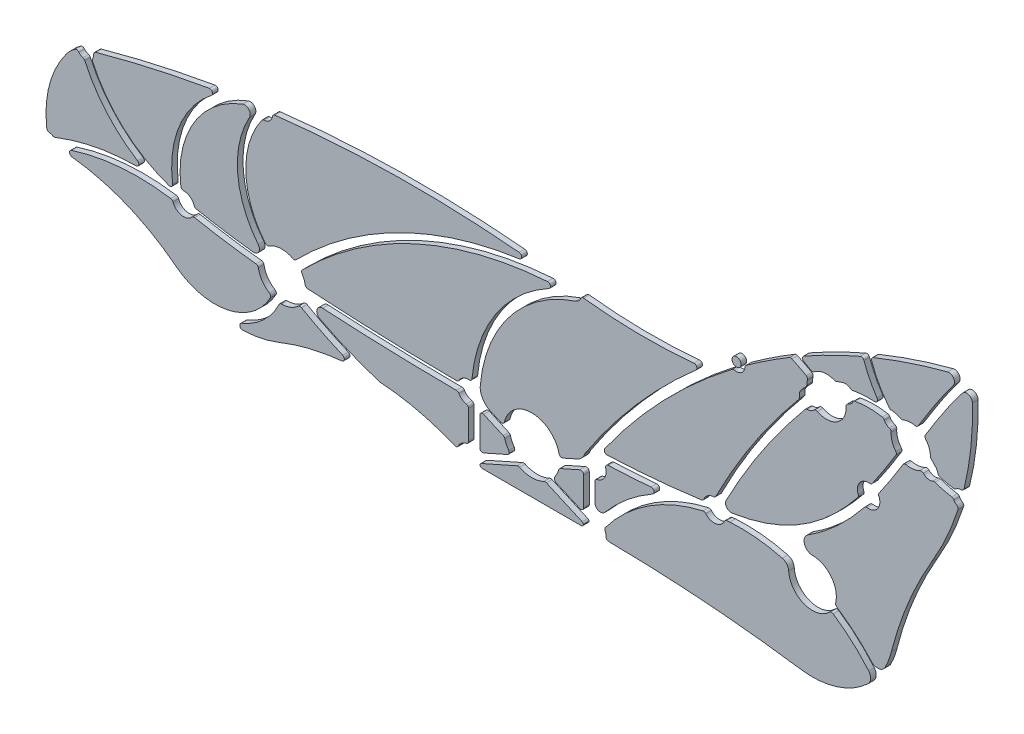
SolidWorks part; units mm, degrees
material "ｴﾎﾟｷｼ樹脂(充填剤なし)"
ref_plane "正面" through (0, 0, 0) normal (0, 0, 1) x (1, 0, 0)
ref_plane "平面" through (0, 0, 0) normal (0, 1, 0) x (1, 0, 0)
ref_plane "右側面" through (0, 0, 0) normal (1, 0, 0) x (0, 0, -1)
sketch "ｽｹｯﾁ1" plane through (0, 0, 0) normal (0, 0, 1) x (1, 0, 0)
  line L1 (-22.5, -10.101) -> (-22.5, 0.101)
  line L2 (-22.5, -10.101) -> (-22.5, 0.101)
  line L3 (22.5, 0.101) -> (22.5, -6.4126)
  line L4 (22.5, 0.101) -> (22.5, -6.4126)
  line L6 (11.119, 1.5832) -> (16.2024, 3.8425)
  line L7 (18.5, -10.042) -> (18.5, 0.042)
  line L8 (8.626, -7.1923) -> (17.0939, -10.9558)
  line L9 (17.0939, 0.9558) -> (10.1663, -2.1231)
  line L10 (18.5, -10.042) -> (18.5, 0.042)
  line L11 (8.626, -7.1923) -> (17.0939, -10.9558)
  line L12 (17.0939, 0.9558) -> (10.1663, -2.1231)
  line L13 (-10.1663, -2.1231) -> (-17.0939, 0.9558)
  line L14 (-17.0939, -10.9558) -> (-8.626, -7.1923)
  line L15 (-18.5, 0.042) -> (-18.5, -10.042)
  line L16 (-10.1663, -2.1231) -> (-17.0939, 0.9558)
  line L17 (-17.0939, -10.9558) -> (-8.626, -7.1923)
  line L18 (-18.5, 0.042) -> (-18.5, -10.042)
  line L19 (-17.5, -16) -> (17.5, -16)
  line L20 (-5.2366, -8.9688) -> (-17.9339, -14.6121)
  line L21 (17.9339, -14.6121) -> (5.2366, -8.9688)
  line L22 (-17.5, -16) -> (17.5, -16)
  line L23 (-5.2366, -8.9688) -> (-17.9339, -14.6121)
  line L24 (17.9339, -14.6121) -> (5.2366, -8.9688)
  line L25 (-14.7807, 3.2107) -> (-11.119, 1.5832)
  line L26 (11.119, 1.5832) -> (16.2024, 3.8425)
  line L27 (-14.7807, 3.2107) -> (-11.119, 1.5832)
  arc A16 (-103.3566, -14.0607) -> (-89.967, -1.5631) centre (-112.8701, 9.5532) ccw
  arc A17 (-89.0603, -0.9998) -> (-89.967, -1.5631) centre (-89.0674, -1.9998) ccw
  arc A18 (-89.0603, -0.9998) -> (-83.2113, 1.2758) centre (-89, 7.5) ccw
  arc A19 (-82.0317, 1.4104) -> (-83.2113, 1.2758) centre (-82.5302, 0.5435) ccw
  arc A20 (-82.0317, 1.4104) -> (-67.3468, -5.898) centre (-13.9413, 119.818) ccw
  arc A21 (-67.6378, -7.8134) -> (-67.3468, -5.898) centre (-67.7378, -6.8184) ccw
  arc A22 (-67.6378, -7.8134) -> (-90.1176, -13.3365) centre (-59.3978, -89.8605) ccw
  arc A23 (-102.9573, -15.9879) -> (-90.1176, -13.3365) centre (-103.9017, 21) ccw
  arc A24 (-103.3566, -14.0607) -> (-102.9573, -15.9879) centre (-102.9829, -14.9883) ccw
  arc A25 (-103.3566, -14.0607) -> (-89.967, -1.5631) centre (-112.8701, 9.5532) ccw
  arc A26 (-89.0603, -0.9998) -> (-89.967, -1.5631) centre (-89.0674, -1.9998) ccw
  arc A27 (-89.0603, -0.9998) -> (-83.2113, 1.2758) centre (-89, 7.5) ccw
  arc A28 (-82.0317, 1.4104) -> (-83.2113, 1.2758) centre (-82.5302, 0.5435) ccw
  arc A29 (-82.0317, 1.4104) -> (-67.3468, -5.898) centre (-13.9413, 119.818) ccw
  arc A30 (-67.6378, -7.8134) -> (-67.3468, -5.898) centre (-67.7378, -6.8184) ccw
  arc A31 (-67.6378, -7.8134) -> (-90.1176, -13.3365) centre (-59.3978, -89.8605) ccw
  arc A32 (-102.9573, -15.9879) -> (-90.1176, -13.3365) centre (-103.9017, 21) ccw
  arc A33 (-103.3566, -14.0607) -> (-102.9573, -15.9879) centre (-102.9829, -14.9883) ccw
  arc A35 (-114.85, 52.6669) -> (-155.2686, 43.5545) centre (-42.29, -363.3692) ccw
  arc A36 (-114.0595, 50.8962) -> (-114.85, 52.6669) centre (-114.6782, 51.6818) ccw
  arc A37 (-114.0595, 50.8962) -> (-127.9008, 16.5808) centre (-91.0356, 21.6602) ccw
  arc A38 (-126.7209, -8.1253) -> (-163.7257, 7.0322) centre (-172, -65.9175) ccw
  arc A39 (-163.9203, 8.9775) -> (-163.7257, 7.0322) centre (-163.613, 8.0259) ccw
  arc A40 (-128.5572, 11.8079) -> (-163.9203, 8.9775) centre (-140.2604, -64.3004) ccw
  arc A41 (-127.7673, 11.1556) -> (-128.5572, 11.8079) centre (-128.7091, 10.8195) ccw
  arc A42 (-127.7673, 11.1556) -> (-121.0036, 9.8502) centre (-124, 12.5) ccw
  arc A43 (-120.0633, 10.1693) -> (-121.0036, 9.8502) centre (-120.2545, 9.1877) ccw
  arc A44 (-120.0633, 10.1693) -> (-98.2474, 6.8503) centre (-69.0994, 271.8045) ccw
  arc A45 (-97.3718, 6.0294) -> (-98.2474, 6.8503) centre (-98.3567, 5.8563) ccw
  arc A46 (-97.3718, 6.0294) -> (-93.4427, 0.2535) centre (-89, 7.5) ccw
  arc A47 (-93.0844, -1.0722) -> (-93.4427, 0.2535) centre (-93.9654, -0.5991) ccw
  arc A48 (-126.7209, -8.1253) -> (-93.0844, -1.0722) centre (-112.8701, 9.5532) ccw
  arc A49 (-126.7209, -8.1253) -> (-163.7257, 7.0322) centre (-172, -65.9175) ccw
  arc A50 (-163.9203, 8.9775) -> (-163.7257, 7.0322) centre (-163.613, 8.0259) ccw
  arc A51 (-128.5572, 11.8079) -> (-163.9203, 8.9775) centre (-140.2604, -64.3004) ccw
  arc A52 (-127.7673, 11.1556) -> (-128.5572, 11.8079) centre (-128.7091, 10.8195) ccw
  arc A53 (-127.7673, 11.1556) -> (-121.0036, 9.8502) centre (-124, 12.5) ccw
  arc A54 (-120.0633, 10.1693) -> (-121.0036, 9.8502) centre (-120.2545, 9.1877) ccw
  arc A55 (-120.0633, 10.1693) -> (-98.2474, 6.8503) centre (-69.0994, 271.8045) ccw
  arc A56 (-97.3718, 6.0294) -> (-98.2474, 6.8503) centre (-98.3567, 5.8563) ccw
  arc A57 (-97.3718, 6.0294) -> (-93.4427, 0.2535) centre (-89, 7.5) ccw
  arc A58 (-93.0844, -1.0722) -> (-93.4427, 0.2535) centre (-93.9654, -0.5991) ccw
  arc A59 (-126.7209, -8.1253) -> (-93.0844, -1.0722) centre (-112.8701, 9.5532) ccw
  arc A60 (-129.2172, 15.4989) -> (-127.9008, 16.5808) centre (-128.8914, 16.4443) ccw
  arc A61 (-156.4002, 40.1644) -> (-129.2172, 15.4989) centre (-114.0417, 59.5347) ccw
  arc A62 (-156.3681, 41.0602) -> (-156.4002, 40.1644) centre (-155.4908, 40.5803) ccw
  arc A63 (-156.3681, 41.0602) -> (-156.0008, 42.5682) centre (-159, 42.5) ccw
  arc A64 (-155.2686, 43.5545) -> (-156.0008, 42.5682) centre (-155.001, 42.5909) ccw
  arc A65 (-114.85, 52.6669) -> (-155.2686, 43.5545) centre (-42.29, -363.3692) ccw
  arc A66 (-114.0595, 50.8962) -> (-114.85, 52.6669) centre (-114.6782, 51.6818) ccw
  arc A67 (-114.0595, 50.8962) -> (-127.9008, 16.5808) centre (-91.0356, 21.6602) ccw
  arc A68 (-129.2172, 15.4989) -> (-127.9008, 16.5808) centre (-128.8914, 16.4443) ccw
  arc A69 (-156.4002, 40.1644) -> (-129.2172, 15.4989) centre (-114.0417, 59.5347) ccw
  arc A70 (-156.3681, 41.0602) -> (-156.4002, 40.1644) centre (-155.4908, 40.5803) ccw
  arc A71 (-156.3681, 41.0602) -> (-156.0008, 42.5682) centre (-159, 42.5) ccw
  arc A72 (-155.2686, 43.5545) -> (-156.0008, 42.5682) centre (-155.001, 42.5909) ccw
  arc A73 (-100.5051, 50.879) -> (-97.4246, 13.2154) centre (-71.0713, 34.3286) ccw
  arc A74 (-99.214, 9.978) -> (-97.4246, 13.2154) centre (-98.9855, 11.9649) ccw
  arc A75 (-4.471, 57.2503) -> (-91.4838, 56.0721) centre (-42.29, -363.3692) ccw
  arc A76 (-140.9263, 15.6997) -> (-169.717, 10.0822) centre (-140.2604, -64.3004) ccw
  arc A77 (-170.5639, 10.1339) -> (-169.717, 10.0822) centre (-170.0852, 11.0119) ccw
  arc A78 (-170.5639, 10.1339) -> (-171.786, 10.4924) centre (-172, 7.5) ccw
  arc A79 (-172.7066, 11.3632) -> (-171.786, 10.4924) centre (-171.7146, 11.4898) ccw
  arc A80 (-165.6353, 37.9447) -> (-172.7066, 11.3632) centre (-136.5587, 15.9784) ccw
  arc A81 (-162.6526, 40.7855) -> (-165.6353, 37.9447) centre (-155.4945, 30.2837) ccw
  arc A82 (-161.317, 40.5944) -> (-162.6526, 40.7855) centre (-162.0894, 39.9592) ccw
  arc A83 (-161.317, 40.5944) -> (-159.8316, 39.6176) centre (-159, 42.5) ccw
  arc A84 (-159.198, 39.0695) -> (-159.8316, 39.6176) centre (-160.1088, 38.6568) ccw
  arc A85 (-159.198, 39.0695) -> (-140.4029, 17.5466) centre (-114.0417, 59.5347) ccw
  arc A86 (-140.9263, 15.6997) -> (-140.4029, 17.5466) centre (-140.9346, 16.6997) ccw
  arc A87 (-140.9263, 15.6997) -> (-169.717, 10.0822) centre (-140.2604, -64.3004) ccw
  arc A88 (-170.5639, 10.1339) -> (-169.717, 10.0822) centre (-170.0852, 11.0119) ccw
  arc A89 (-170.5639, 10.1339) -> (-171.786, 10.4924) centre (-172, 7.5) ccw
  arc A90 (-172.7066, 11.3632) -> (-171.786, 10.4924) centre (-171.7146, 11.4898) ccw
  arc A91 (-165.6353, 37.9447) -> (-172.7066, 11.3632) centre (-136.5587, 15.9784) ccw
  arc A92 (-162.6526, 40.7855) -> (-165.6353, 37.9447) centre (-155.4945, 30.2837) ccw
  arc A93 (-161.317, 40.5944) -> (-162.6526, 40.7855) centre (-162.0894, 39.9592) ccw
  arc A94 (-161.317, 40.5944) -> (-159.8316, 39.6176) centre (-159, 42.5) ccw
  arc A95 (-159.198, 39.0695) -> (-159.8316, 39.6176) centre (-160.1088, 38.6568) ccw
  arc A96 (-159.198, 39.0695) -> (-140.4029, 17.5466) centre (-114.0417, 59.5347) ccw
  arc A97 (-140.9263, 15.6997) -> (-140.4029, 17.5466) centre (-140.9346, 16.6997) ccw
  arc A98 (-4.4224, 55.2639) -> (-4.471, 57.2503) centre (-4.5606, 56.2543) ccw
  arc A99 (-4.4224, 55.2639) -> (-83.9236, 15.238) centre (14.6672, -81.6202) ccw
  arc A100 (-85.0963, 15.0506) -> (-83.9236, 15.238) centre (-84.637, 15.9389) ccw
  arc A101 (-85.0963, 15.0506) -> (-93.5868, 14.6562) centre (-89, 7.5) ccw
  arc A102 (-94.9009, 14.8656) -> (-93.5868, 14.6562) centre (-94.1264, 15.4981) ccw
  arc A103 (-96.1287, 52.1831) -> (-94.9009, 14.8656) centre (-71.0713, 34.3286) ccw
  arc A104 (-95.319, 52.6028) -> (-96.1287, 52.1831) centre (-95.3143, 51.6028) ccw
  arc A105 (-95.319, 52.6028) -> (-92.3587, 55.2099) centre (-95.3328, 55.6027) ccw
  arc A106 (-91.4838, 56.0721) -> (-92.3587, 55.2099) centre (-91.3673, 55.0789) ccw
  arc A107 (-4.471, 57.2503) -> (-91.4838, 56.0721) centre (-42.29, -363.3692) ccw
  arc A108 (-4.4224, 55.2639) -> (-4.471, 57.2503) centre (-4.5606, 56.2543) ccw
  arc A109 (-4.4224, 55.2639) -> (-83.9236, 15.238) centre (14.6672, -81.6202) ccw
  arc A110 (-85.0963, 15.0506) -> (-83.9236, 15.238) centre (-84.637, 15.9389) ccw
  arc A111 (-85.0963, 15.0506) -> (-93.5868, 14.6562) centre (-89, 7.5) ccw
  arc A112 (-94.9009, 14.8656) -> (-93.5868, 14.6562) centre (-94.1264, 15.4981) ccw
  arc A113 (-96.1287, 52.1831) -> (-94.9009, 14.8656) centre (-71.0713, 34.3286) ccw
  arc A114 (-95.319, 52.6028) -> (-96.1287, 52.1831) centre (-95.3143, 51.6028) ccw
  arc A115 (-95.319, 52.6028) -> (-92.3587, 55.2099) centre (-95.3328, 55.6027) ccw
  arc A116 (-91.4838, 56.0721) -> (-92.3587, 55.2099) centre (-91.3673, 55.0789) ccw
  arc A117 (-22.314, 8.9957) -> (-25.9592, 7.0085) centre (-22.5, 5) ccw
  arc A118 (-26.8289, 6.5106) -> (-25.9592, 7.0085) centre (-26.824, 7.5106) ccw
  arc A119 (-79.7472, 8.3552) -> (-26.8289, 6.5106) centre (-22.5, 890.7) ccw
  arc A120 (-80.6633, 9.158) -> (-79.7472, 8.3552) centre (-79.6825, 9.3531) ccw
  arc A121 (-80.6633, 9.158) -> (-81.8017, 12.0204) centre (-89, 7.5) ccw
  arc A122 (-81.6673, 13.2539) -> (-81.8017, 12.0204) centre (-80.9548, 12.5522) ccw
  arc A123 (5.6096, 53.2849) -> (-81.6673, 13.2539) centre (14.6672, -81.6202) ccw
  arc A124 (6.1525, 51.4076) -> (5.6096, 53.2849) centre (5.6766, 52.2871) ccw
  arc A125 (6.1525, 51.4076) -> (-21.2718, 9.9017) centre (31.2679, 5) ccw
  arc A126 (-22.314, 8.9957) -> (-21.2718, 9.9017) centre (-22.2675, 9.9946) ccw
  arc A127 (-22.314, 8.9957) -> (-25.9592, 7.0085) centre (-22.5, 5) ccw
  arc A128 (-26.8289, 6.5106) -> (-25.9592, 7.0085) centre (-26.824, 7.5106) ccw
  arc A129 (-79.7472, 8.3552) -> (-26.8289, 6.5106) centre (-22.5, 890.7) ccw
  arc A130 (-80.6633, 9.158) -> (-79.7472, 8.3552) centre (-79.6825, 9.3531) ccw
  arc A131 (-80.6633, 9.158) -> (-81.8017, 12.0204) centre (-89, 7.5) ccw
  arc A132 (-81.6673, 13.2539) -> (-81.8017, 12.0204) centre (-80.9548, 12.5522) ccw
  arc A133 (5.6096, 53.2849) -> (-81.6673, 13.2539) centre (14.6672, -81.6202) ccw
  arc A134 (6.1525, 51.4076) -> (5.6096, 53.2849) centre (5.6766, 52.2871) ccw
  arc A135 (6.1525, 51.4076) -> (-21.2718, 9.9017) centre (31.2679, 5) ccw
  arc A136 (-22.314, 8.9957) -> (-21.2718, 9.9017) centre (-22.2675, 9.9946) ccw
  arc A137 (-119.4498, 13.1062) -> (-99.214, 9.978) centre (-69.0994, 271.8045) ccw
  arc A138 (-27.4366, -13.8466) -> (-54.0639, -7.5734) centre (-59.3978, -89.8605) ccw
  arc A139 (-54.3014, -7.5287) -> (-54.0639, -7.5734) centre (-53.9993, -6.5755) ccw
  arc A140 (-75.487, 1.2505) -> (-54.3014, -7.5287) centre (-13.9413, 119.818) ccw
  arc A141 (-74.4485, 5.0222) -> (-75.487, 1.2505) centre (-74.5656, 3.0256) ccw
  arc A142 (-74.4485, 5.0222) -> (-26.8313, 3.5106) centre (-22.5, 890.7) ccw
  arc A143 (-25.969, 3.0085) -> (-26.8313, 3.5106) centre (-26.8362, 2.5106) ccw
  arc A144 (-25.969, 3.0085) -> (-23.3, 1.0808) centre (-22.5, 5) ccw
  arc A145 (-22.5, 0.101) -> (-23.3, 1.0808) centre (-23.5, 0.101) ccw
  arc A146 (-23.3, -11.0808) -> (-22.5, -10.101) centre (-23.5, -10.101) ccw
  arc A147 (-23.3, -11.0808) -> (-26.1392, -13.3399) centre (-22.5, -15) ccw
  arc A148 (-27.4366, -13.8466) -> (-26.1392, -13.3399) centre (-27.049, -12.9248) ccw
  arc A149 (-27.4366, -13.8466) -> (-54.0639, -7.5734) centre (-59.3978, -89.8605) ccw
  arc A150 (-54.3014, -7.5287) -> (-54.0639, -7.5734) centre (-53.9993, -6.5755) ccw
  arc A151 (-75.487, 1.2505) -> (-54.3014, -7.5287) centre (-13.9413, 119.818) ccw
  arc A152 (-74.4485, 5.0222) -> (-75.487, 1.2505) centre (-74.5656, 3.0256) ccw
  arc A153 (-74.4485, 5.0222) -> (-26.8313, 3.5106) centre (-22.5, 890.7) ccw
  arc A154 (-25.969, 3.0085) -> (-26.8313, 3.5106) centre (-26.8362, 2.5106) ccw
  arc A155 (-25.969, 3.0085) -> (-23.3, 1.0808) centre (-22.5, 5) ccw
  arc A156 (-22.5, 0.101) -> (-23.3, 1.0808) centre (-23.5, 0.101) ccw
  arc A157 (-23.3, -11.0808) -> (-22.5, -10.101) centre (-23.5, -10.101) ccw
  arc A158 (-23.3, -11.0808) -> (-26.1392, -13.3399) centre (-22.5, -15) ccw
  arc A159 (-27.4366, -13.8466) -> (-26.1392, -13.3399) centre (-27.049, -12.9248) ccw
  arc A160 (-120.207, 13.7702) -> (-119.4498, 13.1062) centre (-119.2588, 14.0878) ccw
  arc A161 (-120.207, 13.7702) -> (-123.99, 16.5) centre (-124, 12.5) ccw
  arc A162 (-124.9796, 17.3747) -> (-123.99, 16.5) centre (-123.9875, 17.5) ccw
  arc A163 (-102.9446, 53.7342) -> (-124.9796, 17.3747) centre (-91.0356, 21.6602) ccw
  arc A164 (-100.5051, 50.879) -> (-102.9446, 53.7342) centre (-102.2484, 51.8592) ccw
  arc A165 (-100.5051, 50.879) -> (-97.4246, 13.2154) centre (-71.0713, 34.3286) ccw
  arc A166 (-99.214, 9.978) -> (-97.4246, 13.2154) centre (-98.9855, 11.9649) ccw
  arc A167 (-119.4498, 13.1062) -> (-99.214, 9.978) centre (-69.0994, 271.8045) ccw
  arc A168 (-120.207, 13.7702) -> (-119.4498, 13.1062) centre (-119.2588, 14.0878) ccw
  arc A169 (-120.207, 13.7702) -> (-123.99, 16.5) centre (-124, 12.5) ccw
  arc A170 (-124.9796, 17.3747) -> (-123.99, 16.5) centre (-123.9875, 17.5) ccw
  arc A171 (-102.9446, 53.7342) -> (-124.9796, 17.3747) centre (-91.0356, 21.6602) ccw
  arc A172 (-100.5051, 50.879) -> (-102.9446, 53.7342) centre (-102.2484, 51.8592) ccw
  arc A180 (17.0939, -10.9558) -> (18.5, -10.042) centre (17.5, -10.042) ccw
  arc A181 (8.2111, -5.7077) -> (8.626, -7.1923) centre (9.0322, -6.2785) ccw
  arc A182 (22.5, -6.4126) -> (26.0294, -7.7013) centre (24.5, -6.4126) ccw
  arc A183 (23.3, 1.0808) -> (22.5, 0.101) centre (23.5, 0.101) ccw
  arc A184 (23.3, 1.0808) -> (26.3403, 6.1191) centre (22.5, 5) ccw
  arc A185 (27.2601, 7.398) -> (26.3403, 6.1191) centre (27.3003, 6.3988) ccw
  arc A186 (27.2601, 7.398) -> (42.5161, 8.3479) centre (13.2682, 355.1295) ccw
  arc A187 (43.0938, 6.4818) -> (42.5161, 8.3479) centre (42.6001, 7.3514) ccw
  arc A188 (107.7452, 73.9205) -> (100.6016, 72.9268) centre (105, 67.4812) ccw
  arc A189 (99.4771, 72.8365) -> (100.6016, 72.9268) centre (99.9733, 73.7047) ccw
  arc A190 (99.4771, 72.8365) -> (96.9768, 74.198) centre (65, 12.5) ccw
  arc A191 (96.9469, 75.9576) -> (96.9768, 74.198) centre (97.4369, 75.0859) ccw
  arc A192 (116.993, 85.9037) -> (96.9469, 75.9576) centre (203.2901, -113.1988) ccw
  arc A193 (118.3344, 85.3171) -> (116.993, 85.9037) centre (117.3907, 84.9862) ccw
  arc A194 (118.3344, 85.3171) -> (122.9876, 76.0572) centre (156.5, 98.6967) ccw
  arc A195 (122.0896, 74.4999) -> (122.9876, 76.0572) centre (122.1589, 75.4974) ccw
  arc A196 (122.0896, 74.4999) -> (114.3306, 74.0344) centre (120, 44.4324) ccw
  arc A197 (113.5331, 74.2236) -> (114.3306, 74.0344) centre (114.1425, 75.0165) ccw
  arc A198 (113.5331, 74.2236) -> (110.8362, 74.7163) centre (111.7051, 71.8449) ccw
  arc A199 (110.8362, 74.7163) -> (108.5008, 73.9088) centre (120, 44.4324) ccw
  arc A200 (107.7452, 73.9205) -> (108.5008, 73.9088) centre (108.1373, 74.8404) ccw
  arc A201 (107.7452, 73.9205) -> (100.6016, 72.9268) centre (105, 67.4812) ccw
  arc A202 (99.4771, 72.8365) -> (100.6016, 72.9268) centre (99.9733, 73.7047) ccw
  arc A203 (99.4771, 72.8365) -> (96.9768, 74.198) centre (65, 12.5) ccw
  arc A204 (96.9469, 75.9576) -> (96.9768, 74.198) centre (97.4369, 75.0859) ccw
  arc A205 (116.993, 85.9037) -> (96.9469, 75.9576) centre (203.2901, -113.1988) ccw
  arc A206 (118.3344, 85.3171) -> (116.993, 85.9037) centre (117.3907, 84.9862) ccw
  arc A207 (118.3344, 85.3171) -> (122.9876, 76.0572) centre (156.5, 98.6967) ccw
  arc A208 (122.0896, 74.4999) -> (122.9876, 76.0572) centre (122.1589, 75.4974) ccw
  arc A209 (122.0896, 74.4999) -> (114.3306, 74.0344) centre (120, 44.4324) ccw
  arc A210 (113.5331, 74.2236) -> (114.3306, 74.0344) centre (114.1425, 75.0165) ccw
  arc A211 (113.5331, 74.2236) -> (110.8362, 74.7163) centre (111.7051, 71.8449) ccw
  arc A212 (110.8362, 74.7163) -> (108.5008, 73.9088) centre (120, 44.4324) ccw
  arc A213 (107.7452, 73.9205) -> (108.5008, 73.9088) centre (108.1373, 74.8404) ccw
  arc A214 (43.0938, 6.4818) -> (26.0294, -7.7013) centre (74.1755, -48.2713) ccw
  arc A215 (22.5, -6.4126) -> (26.0294, -7.7013) centre (24.5, -6.4126) ccw
  arc A216 (23.3, 1.0808) -> (22.5, 0.101) centre (23.5, 0.101) ccw
  arc A217 (23.3, 1.0808) -> (26.3403, 6.1191) centre (22.5, 5) ccw
  arc A218 (89.2736, 9.7568) -> (70.6226, 11.5834) centre (74.1755, -48.2713) ccw
  arc A219 (91.5134, 7.0221) -> (89.2736, 9.7568) centre (88.5182, 6.8535) ccw
  arc A220 (91.5134, 7.0221) -> (106.0705, 1.5503) centre (100, 7.5) ccw
  arc A221 (107.3377, 1.6835) -> (106.0705, 1.5503) centre (106.7847, 0.8503) ccw
  arc A222 (120.0008, -9.6028) -> (107.3377, 1.6835) centre (74.1755, -48.2713) ccw
  arc A223 (119.7512, -13.7341) -> (120.0008, -9.6028) centre (117.708, -11.5375) ccw
  arc A224 (95.9045, -21.2094) -> (119.7512, -13.7341) centre (100, 7.5) ccw
  arc A225 (95.9045, -21.2094) -> (27.4903, -16.024) centre (22.5, -535.7727) ccw
  arc A226 (26.5, -15.0192) -> (27.4903, -16.024) centre (27.4999, -15.024) ccw
  arc A227 (26.5, -15.0192) -> (26.1198, -13.2978) centre (22.5, -15) ccw
  arc A228 (26.225, -12.2719) -> (26.1198, -13.2978) centre (27.0247, -12.8723) ccw
  arc A229 (60.9851, 10.2199) -> (26.225, -12.2719) centre (74.1755, -48.2713) ccw
  arc A230 (61.9641, 9.8955) -> (60.9851, 10.2199) centre (61.2051, 9.2444) ccw
  arc A231 (61.9641, 9.8955) -> (68.6438, 10.85) centre (65, 12.5) ccw
  arc A232 (69.4318, 11.4299) -> (68.6438, 10.85) centre (69.5548, 10.4374) ccw
  arc A233 (69.4318, 11.4299) -> (70.5449, 11.5758) centre (59.6347, 90.4932) ccw
  arc A234 (70.6226, 11.5834) -> (70.5449, 11.5758) centre (70.6819, 10.5852) ccw
  arc A235 (89.2736, 9.7568) -> (70.6226, 11.5834) centre (74.1755, -48.2713) ccw
  arc A236 (91.5134, 7.0221) -> (89.2736, 9.7568) centre (88.5182, 6.8535) ccw
  arc A237 (91.5134, 7.0221) -> (106.0705, 1.5503) centre (100, 7.5) ccw
  arc A238 (107.3377, 1.6835) -> (106.0705, 1.5503) centre (106.7847, 0.8503) ccw
  arc A239 (120.0008, -9.6028) -> (107.3377, 1.6835) centre (74.1755, -48.2713) ccw
  arc A240 (119.7512, -13.7341) -> (120.0008, -9.6028) centre (117.708, -11.5375) ccw
  arc A241 (95.9045, -21.2094) -> (119.7512, -13.7341) centre (100, 7.5) ccw
  arc A242 (95.9045, -21.2094) -> (27.4903, -16.024) centre (22.5, -535.7727) ccw
  arc A243 (26.5, -15.0192) -> (27.4903, -16.024) centre (27.4999, -15.024) ccw
  arc A244 (26.5, -15.0192) -> (26.1198, -13.2978) centre (22.5, -15) ccw
  arc A245 (26.225, -12.2719) -> (26.1198, -13.2978) centre (27.0247, -12.8723) ccw
  arc A246 (60.9851, 10.2199) -> (26.225, -12.2719) centre (74.1755, -48.2713) ccw
  arc A247 (61.9641, 9.8955) -> (60.9851, 10.2199) centre (61.2051, 9.2444) ccw
  arc A248 (61.9641, 9.8955) -> (68.6438, 10.85) centre (65, 12.5) ccw
  arc A249 (69.4318, 11.4299) -> (68.6438, 10.85) centre (69.5548, 10.4374) ccw
  arc A250 (69.4318, 11.4299) -> (70.5449, 11.5758) centre (59.6347, 90.4932) ccw
  arc A251 (70.6226, 11.5834) -> (70.5449, 11.5758) centre (70.6819, 10.5852) ccw
  arc A252 (27.2601, 7.398) -> (26.3403, 6.1191) centre (27.3003, 6.3988) ccw
  arc A253 (27.2601, 7.398) -> (42.5161, 8.3479) centre (13.2682, 355.1295) ccw
  arc A254 (71.3431, 59.0772) -> (26.022, 11.9612) centre (203.2901, -113.1988) ccw
  arc A255 (72.1979, 59.2524) -> (71.3431, 59.0772) centre (71.9512, 58.2833) ccw
  arc A256 (72.1979, 59.2524) -> (75.9352, 62.0305) centre (72.938, 62.1596) ccw
  arc A257 (76.3493, 62.7985) -> (75.9352, 62.0305) centre (76.9343, 61.9874) ccw
  arc A258 (91.7165, 72.9204) -> (76.3493, 62.7985) centre (203.2901, -113.1988) ccw
  arc A259 (92.6465, 72.9722) -> (91.7165, 72.9204) centre (92.2307, 72.0627) ccw
  arc A260 (97.7506, 70.3671) -> (92.6465, 72.9722) centre (65, 12.5) ccw
  arc A261 (98.2258, 69.2449) -> (97.7506, 70.3671) centre (97.2581, 69.4969) ccw
  arc A262 (98.2258, 69.2449) -> (98.0007, 67.5789) centre (105, 67.4812) ccw
  arc A263 (97.7054, 66.8832) -> (98.0007, 67.5789) centre (97.0008, 67.5928) ccw
  arc A264 (97.7054, 66.8832) -> (96.0213, 65.0748) centre (120, 44.4324) ccw
  arc A265 (96.0213, 65.0748) -> (95.3497, 62.5466) centre (98.2949, 63.1176) ccw
  arc A266 (95.1344, 61.7139) -> (95.3497, 62.5466) centre (94.368, 62.3562) ccw
  arc A267 (95.1344, 61.7139) -> (65.5834, 17.0366) centre (276.8279, -90.5756) ccw
  arc A268 (64.7539, 16.4924) -> (65.5834, 17.0366) centre (64.6924, 17.4905) ccw
  arc A269 (64.7539, 16.4924) -> (61.2853, 13.9837) centre (65, 12.5) ccw
  arc A270 (60.4936, 13.364) -> (61.2853, 13.9837) centre (60.3567, 14.3546) ccw
  arc A271 (26.8783, 10.3852) -> (60.4936, 13.364) centre (13.2682, 355.1295) ccw
  arc A272 (26.022, 11.9612) -> (26.8783, 10.3852) centre (26.8389, 11.3844) ccw
  arc A273 (71.3431, 59.0772) -> (26.022, 11.9612) centre (203.2901, -113.1988) ccw
  arc A274 (72.1979, 59.2524) -> (71.3431, 59.0772) centre (71.9512, 58.2833) ccw
  arc A275 (72.1979, 59.2524) -> (75.9352, 62.0305) centre (72.938, 62.1596) ccw
  arc A276 (76.3493, 62.7985) -> (75.9352, 62.0305) centre (76.9343, 61.9874) ccw
  arc A277 (91.7165, 72.9204) -> (76.3493, 62.7985) centre (203.2901, -113.1988) ccw
  arc A278 (92.6465, 72.9722) -> (91.7165, 72.9204) centre (92.2307, 72.0627) ccw
  arc A279 (97.7506, 70.3671) -> (92.6465, 72.9722) centre (65, 12.5) ccw
  arc A280 (98.2258, 69.2449) -> (97.7506, 70.3671) centre (97.2581, 69.4969) ccw
  arc A281 (98.2258, 69.2449) -> (98.0007, 67.5789) centre (105, 67.4812) ccw
  arc A282 (97.7054, 66.8832) -> (98.0007, 67.5789) centre (97.0008, 67.5928) ccw
  arc A283 (97.7054, 66.8832) -> (96.0213, 65.0748) centre (120, 44.4324) ccw
  arc A284 (96.0213, 65.0748) -> (95.3497, 62.5466) centre (98.2949, 63.1176) ccw
  arc A285 (95.1344, 61.7139) -> (95.3497, 62.5466) centre (94.368, 62.3562) ccw
  arc A286 (95.1344, 61.7139) -> (65.5834, 17.0366) centre (276.8279, -90.5756) ccw
  arc A287 (64.7539, 16.4924) -> (65.5834, 17.0366) centre (64.6924, 17.4905) ccw
  arc A288 (64.7539, 16.4924) -> (61.2853, 13.9837) centre (65, 12.5) ccw
  arc A289 (60.4936, 13.364) -> (61.2853, 13.9837) centre (60.3567, 14.3546) ccw
  arc A290 (26.8783, 10.3852) -> (60.4936, 13.364) centre (13.2682, 355.1295) ccw
  arc A291 (26.022, 11.9612) -> (26.8783, 10.3852) centre (26.8389, 11.3844) ccw
  arc A292 (43.0938, 6.4818) -> (42.5161, 8.3479) centre (42.6001, 7.3514) ccw
  arc A293 (43.0938, 6.4818) -> (26.0294, -7.7013) centre (74.1755, -48.2713) ccw
  arc A294 (8.2111, -5.7077) -> (9.6113, -2.7608) centre (0, 0) ccw
  arc A295 (10.1663, -2.1231) -> (9.6113, -2.7608) centre (10.5725, -3.0369) ccw
  arc A296 (18.5, 0.042) -> (17.0939, 0.9558) centre (17.5, 0.042) ccw
  arc A297 (148.0871, 96.6622) -> (121.6343, 87.8518) centre (203.2901, -113.1988) ccw
  arc A298 (150.1845, 93.5129) -> (148.0871, 96.6622) centre (148.5959, 94.728) ccw
  arc A302 (136.5337, 74.3112) -> (137.605, 74.7637) centre (136.7528, 75.2869) ccw
  arc A303 (136.5337, 74.3112) -> (132.2548, 73.9205) centre (135, 67.4812) ccw
  arc A304 (131.4992, 73.9088) -> (132.2548, 73.9205) centre (131.8627, 74.8404) ccw
  arc A305 (131.4992, 73.9088) -> (129.1638, 74.7163) centre (120, 44.4324) ccw
  arc A306 (129.1638, 74.7163) -> (128.1602, 74.8418) centre (128.2949, 71.8449) ccw
  arc A307 (127.3364, 75.2137) -> (128.1602, 74.8418) centre (128.1152, 75.8408) ccw
  arc A308 (69.2612, 17.6244) -> (71.3386, 14.7231) centre (71.0347, 16.6999) ccw
  arc A309 (97.4124, 59.7615) -> (69.2612, 17.6244) centre (276.8279, -90.5756) ccw
  arc A310 (98.2079, 60.1189) -> (97.4124, 59.7615) centre (98.1789, 59.1193) ccw
  arc A311 (98.2079, 60.1189) -> (100.5079, 61.0921) centre (98.2949, 63.1176) ccw
  arc A312 (101.7149, 61.3) -> (100.5079, 61.0921) centre (101.2456, 60.4169) ccw
  arc A313 (101.7149, 61.3) -> (111.9821, 67.9818) centre (105, 67.4812) ccw
  arc A314 (112.6609, 69.0012) -> (111.9821, 67.9818) centre (112.9795, 68.0533) ccw
  arc A315 (112.6609, 69.0012) -> (114.4231, 70.575) centre (111.7051, 71.8449) ccw
  arc A316 (115.1504, 71.1356) -> (114.4231, 70.575) centre (115.3291, 70.1517) ccw
  arc A317 (124.8496, 71.1356) -> (115.1504, 71.1356) centre (120, 44.4324) ccw
  arc A318 (125.5769, 70.575) -> (124.8496, 71.1356) centre (124.6709, 70.1517) ccw
  arc A319 (125.5769, 70.575) -> (127.3391, 69.0012) centre (128.2949, 71.8449) ccw
  arc A320 (128.0179, 67.9818) -> (127.3391, 69.0012) centre (127.0205, 68.0533) ccw
  arc A321 (128.0179, 67.9818) -> (129.6405, 62.9784) centre (135, 67.4812) ccw
  arc A322 (129.7265, 61.811) -> (129.6405, 62.9784) centre (128.8749, 62.3351) ccw
  arc A323 (120.3745, 48.4148) -> (121.2864, 48.8356) centre (120.4681, 49.4104) ccw
  arc A324 (120.3745, 48.4148) -> (116.2864, 42.9461) centre (120, 44.4324) ccw
  arc A325 (116.1386, 41.9495) -> (116.2864, 42.9461) centre (115.358, 42.5745) ccw
  arc A326 (69.2612, 17.6244) -> (71.3386, 14.7231) centre (71.0347, 16.6999) ccw
  arc A327 (97.4124, 59.7615) -> (69.2612, 17.6244) centre (276.8279, -90.5756) ccw
  arc A328 (98.2079, 60.1189) -> (97.4124, 59.7615) centre (98.1789, 59.1193) ccw
  arc A329 (98.2079, 60.1189) -> (100.5079, 61.0921) centre (98.2949, 63.1176) ccw
  arc A330 (101.7149, 61.3) -> (100.5079, 61.0921) centre (101.2456, 60.4169) ccw
  arc A331 (101.7149, 61.3) -> (111.9821, 67.9818) centre (105, 67.4812) ccw
  arc A332 (112.6609, 69.0012) -> (111.9821, 67.9818) centre (112.9795, 68.0533) ccw
  arc A333 (112.6609, 69.0012) -> (114.4231, 70.575) centre (111.7051, 71.8449) ccw
  arc A334 (115.1504, 71.1356) -> (114.4231, 70.575) centre (115.3291, 70.1517) ccw
  arc A335 (124.8496, 71.1356) -> (115.1504, 71.1356) centre (120, 44.4324) ccw
  arc A336 (125.5769, 70.575) -> (124.8496, 71.1356) centre (124.6709, 70.1517) ccw
  arc A337 (125.5769, 70.575) -> (127.3391, 69.0012) centre (128.2949, 71.8449) ccw
  arc A338 (128.0179, 67.9818) -> (127.3391, 69.0012) centre (127.0205, 68.0533) ccw
  arc A339 (128.0179, 67.9818) -> (129.6405, 62.9784) centre (135, 67.4812) ccw
  arc A340 (129.7265, 61.811) -> (129.6405, 62.9784) centre (128.8749, 62.3351) ccw
  arc A341 (120.3745, 48.4148) -> (121.2864, 48.8356) centre (120.4681, 49.4104) ccw
  arc A342 (120.3745, 48.4148) -> (116.2864, 42.9461) centre (120, 44.4324) ccw
  arc A343 (116.1386, 41.9495) -> (116.2864, 42.9461) centre (115.358, 42.5745) ccw
  arc A344 (121.0642, 86.6023) -> (127.3364, 75.2137) centre (156.5, 98.6967) ccw
  arc A345 (121.6343, 87.8518) -> (121.0642, 86.6023) centre (122.0106, 86.9253) ccw
  arc A346 (148.0871, 96.6622) -> (121.6343, 87.8518) centre (203.2901, -113.1988) ccw
  arc A347 (150.1845, 93.5129) -> (148.0871, 96.6622) centre (148.5959, 94.728) ccw
  arc A348 (136.5337, 74.3112) -> (137.605, 74.7637) centre (136.7528, 75.2869) ccw
  arc A349 (136.5337, 74.3112) -> (132.2548, 73.9205) centre (135, 67.4812) ccw
  arc A350 (131.4992, 73.9088) -> (132.2548, 73.9205) centre (131.8627, 74.8404) ccw
  arc A351 (131.4992, 73.9088) -> (129.1638, 74.7163) centre (120, 44.4324) ccw
  arc A352 (129.1638, 74.7163) -> (128.1602, 74.8418) centre (128.2949, 71.8449) ccw
  arc A353 (127.3364, 75.2137) -> (128.1602, 74.8418) centre (128.1152, 75.8408) ccw
  arc A354 (121.0642, 86.6023) -> (127.3364, 75.2137) centre (156.5, 98.6967) ccw
  arc A355 (121.6343, 87.8518) -> (121.0642, 86.6023) centre (122.0106, 86.9253) ccw
  arc A356 (17.0939, -10.9558) -> (18.5, -10.042) centre (17.5, -10.042) ccw
  arc A357 (8.2111, -5.7077) -> (8.626, -7.1923) centre (9.0322, -6.2785) ccw
  arc A358 (8.2111, -5.7077) -> (9.6113, -2.7608) centre (0, 0) ccw
  arc A359 (10.1663, -2.1231) -> (9.6113, -2.7608) centre (10.5725, -3.0369) ccw
  arc A360 (18.5, 0.042) -> (17.0939, 0.9558) centre (17.5, 0.042) ccw
  arc A361 (-9.6113, -2.7608) -> (-10.1663, -2.1231) centre (-10.5725, -3.0369) ccw
  arc A362 (-9.6113, -2.7608) -> (-8.2111, -5.7077) centre (0, 0) ccw
  arc A363 (-8.626, -7.1923) -> (-8.2111, -5.7077) centre (-9.0322, -6.2785) ccw
  arc A364 (-18.5, -10.042) -> (-17.0939, -10.9558) centre (-17.5, -10.042) ccw
  arc A365 (-17.0939, 0.9558) -> (-18.5, 0.042) centre (-17.5, 0.042) ccw
  arc A366 (-9.6113, -2.7608) -> (-10.1663, -2.1231) centre (-10.5725, -3.0369) ccw
  arc A367 (-9.6113, -2.7608) -> (-8.2111, -5.7077) centre (0, 0) ccw
  arc A368 (-8.626, -7.1923) -> (-8.2111, -5.7077) centre (-9.0322, -6.2785) ccw
  arc A369 (-18.5, -10.042) -> (-17.0939, -10.9558) centre (-17.5, -10.042) ccw
  arc A370 (-17.0939, 0.9558) -> (-18.5, 0.042) centre (-17.5, 0.042) ccw
  circle A371 centre (72.938, 62.1596) radius 1.6
  circle A372 centre (72.938, 62.1596) radius 1.6
  arc A373 (18.4772, -15.2121) -> (17.9339, -14.6121) centre (17.5277, -15.5259) ccw
  arc A374 (17.5, -16) -> (18.4772, -15.2121) centre (17.5, -15) ccw
  arc A375 (-18.4772, -15.2121) -> (-17.5, -16) centre (-17.5, -15) ccw
  arc A376 (-17.9339, -14.6121) -> (-18.4772, -15.2121) centre (-17.5277, -15.5259) ccw
  arc A377 (-4.3913, -8.9842) -> (-5.2366, -8.9688) centre (-4.8304, -9.8827) ccw
  arc A378 (-4.3913, -8.9842) -> (4.3913, -8.9842) centre (0, 0) ccw
  arc A379 (5.2366, -8.9688) -> (4.3913, -8.9842) centre (4.8304, -9.8827) ccw
  arc A380 (18.4772, -15.2121) -> (17.9339, -14.6121) centre (17.5277, -15.5259) ccw
  arc A381 (17.5, -16) -> (18.4772, -15.2121) centre (17.5, -15) ccw
  arc A382 (-18.4772, -15.2121) -> (-17.5, -16) centre (-17.5, -15) ccw
  arc A383 (-17.9339, -14.6121) -> (-18.4772, -15.2121) centre (-17.5277, -15.5259) ccw
  arc A384 (-4.3913, -8.9842) -> (-5.2366, -8.9688) centre (-4.8304, -9.8827) ccw
  arc A385 (-4.3913, -8.9842) -> (4.3913, -8.9842) centre (0, 0) ccw
  arc A386 (5.2366, -8.9688) -> (4.3913, -8.9842) centre (4.8304, -9.8827) ccw
  arc A392 (15.611, 52.2409) -> (17.4557, 53.9822) centre (14.6672, 55.0886) ccw
  arc A393 (18.4998, 54.6068) -> (17.4557, 53.9822) centre (18.3852, 53.6134) ccw
  arc A394 (18.4998, 54.6068) -> (57.7478, 54.1867) centre (40.1338, 242.1889) ccw
  arc A395 (58.4992, 52.4382) -> (57.7478, 54.1867) centre (57.841, 53.1911) ccw
  arc A396 (58.4992, 52.4382) -> (19.152, 7.1889) centre (203.2901, -113.1988) ccw
  arc A397 (19.152, 7.1889) -> (18.7985, 6.5163) centre (22.5, 5) ccw
  arc A398 (16.2024, 3.8425) -> (18.7985, 6.5163) centre (14.1717, 8.4116) ccw
  arc A399 (9.7389, 2.27) -> (11.119, 1.5832) centre (10.7128, 2.4971) ccw
  arc A400 (9.7389, 2.27) -> (-9.7389, 2.27) centre (0, 0) ccw
  arc A401 (-11.119, 1.5832) -> (-9.7389, 2.27) centre (-10.7128, 2.4971) ccw
  arc A402 (-18.3225, 9.1999) -> (-14.7807, 3.2107) centre (-12.3439, 8.6935) ccw
  arc A403 (15.611, 52.2409) -> (-18.3225, 9.1999) centre (31.2679, 5) ccw
  arc A404 (15.611, 52.2409) -> (17.4557, 53.9822) centre (14.6672, 55.0886) ccw
  arc A405 (18.4998, 54.6068) -> (17.4557, 53.9822) centre (18.3852, 53.6134) ccw
  arc A406 (18.4998, 54.6068) -> (57.7478, 54.1867) centre (40.1338, 242.1889) ccw
  arc A407 (58.4992, 52.4382) -> (57.7478, 54.1867) centre (57.841, 53.1911) ccw
  arc A408 (58.4992, 52.4382) -> (19.152, 7.1889) centre (203.2901, -113.1988) ccw
  arc A409 (19.152, 7.1889) -> (18.7985, 6.5163) centre (22.5, 5) ccw
  arc A410 (16.2024, 3.8425) -> (18.7985, 6.5163) centre (14.1717, 8.4116) ccw
  arc A411 (9.7389, 2.27) -> (11.119, 1.5832) centre (10.7128, 2.4971) ccw
  arc A412 (9.7389, 2.27) -> (-9.7389, 2.27) centre (0, 0) ccw
  arc A413 (-11.119, 1.5832) -> (-9.7389, 2.27) centre (-10.7128, 2.4971) ccw
  arc A414 (-18.3225, 9.1999) -> (-14.7807, 3.2107) centre (-12.3439, 8.6935) ccw
  arc A415 (15.611, 52.2409) -> (-18.3225, 9.1999) centre (31.2679, 5) ccw
  arc A416 (153.9743, 63.4967) -> (156.9544, 91.5668) centre (52.35, 88.479) ccw
  arc A417 (152.9962, 62.7355) -> (153.9743, 63.4967) centre (153.0032, 63.7354) ccw
  arc A418 (152.9962, 62.7355) -> (151.0229, 62.0134) centre (152.9752, 59.7355) ccw
  arc A419 (150.204, 61.7869) -> (151.0229, 62.0134) centre (150.3722, 62.7727) ccw
  arc A420 (145.3266, 62.9598) -> (150.204, 61.7869) centre (156.5, 98.6967) ccw
  arc A421 (144.645, 63.7151) -> (145.3266, 62.9598) centre (145.625, 63.9142) ccw
  arc A422 (144.645, 63.7151) -> (143.9787, 65.0748) centre (141.7051, 63.1176) ccw
  arc A423 (143.9787, 65.0748) -> (142.2946, 66.8832) centre (120, 44.4324) ccw
  arc A424 (141.9993, 67.5789) -> (142.2946, 66.8832) centre (142.9992, 67.5928) ccw
  arc A425 (141.9993, 67.5789) -> (140.2901, 72.0654) centre (135, 67.4812) ccw
  arc A426 (140.1936, 73.2435) -> (140.2901, 72.0654) centre (141.0458, 72.7203) ccw
  arc A427 (156.9544, 91.5668) -> (153.3792, 92.7391) centre (154.9553, 91.5078) ccw
  arc A428 (153.9743, 63.4967) -> (156.9544, 91.5668) centre (52.35, 88.479) ccw
  arc A429 (152.9962, 62.7355) -> (153.9743, 63.4967) centre (153.0032, 63.7354) ccw
  arc A430 (152.9962, 62.7355) -> (151.0229, 62.0134) centre (152.9752, 59.7355) ccw
  arc A431 (150.204, 61.7869) -> (151.0229, 62.0134) centre (150.3722, 62.7727) ccw
  arc A432 (145.3266, 62.9598) -> (150.204, 61.7869) centre (156.5, 98.6967) ccw
  arc A433 (144.645, 63.7151) -> (145.3266, 62.9598) centre (145.625, 63.9142) ccw
  arc A434 (144.645, 63.7151) -> (143.9787, 65.0748) centre (141.7051, 63.1176) ccw
  arc A435 (143.9787, 65.0748) -> (142.2946, 66.8832) centre (120, 44.4324) ccw
  arc A436 (141.9993, 67.5789) -> (142.2946, 66.8832) centre (142.9992, 67.5928) ccw
  arc A437 (141.9993, 67.5789) -> (140.2901, 72.0654) centre (135, 67.4812) ccw
  arc A438 (140.1936, 73.2435) -> (140.2901, 72.0654) centre (141.0458, 72.7203) ccw
  arc A439 (156.9544, 91.5668) -> (153.3792, 92.7391) centre (154.9553, 91.5078) ccw
  arc A448 (143.571, 60.3761) -> (149.6129, 58.8445) centre (156.5, 98.6967) ccw
  arc A449 (150.3258, 58.3282) -> (149.6129, 58.8445) centre (149.4426, 57.8591) ccw
  arc A450 (150.3258, 58.3282) -> (151.4085, 57.1771) centre (152.9752, 59.7355) ccw
  arc A451 (151.8369, 56.0141) -> (151.4085, 57.1771) centre (150.8863, 56.3243) ccw
  arc A452 (142.5363, 35.3937) -> (151.8369, 56.0141) centre (52.35, 88.479) ccw
  arc A453 (142.5363, 35.3937) -> (128.1038, 0.346) centre (258.447, -32.8336) ccw
  arc A454 (125.9109, -5.5239) -> (128.1038, 0.346) centre (100, 7.5) ccw
  arc A455 (120.9994, -6.1821) -> (125.9109, -5.5239) centre (123.2305, -4.1766) ccw
  arc A456 (120.9994, -6.1821) -> (108.6769, 4.3939) centre (74.1755, -48.2713) ccw
  arc A457 (108.2539, 5.4693) -> (108.6769, 4.3939) centre (109.2249, 5.2304) ccw
  arc A463 (108.2539, 5.4693) -> (100.0042, 16) centre (100, 7.5) ccw
  arc A464 (98.4004, 21.5344) -> (100.0042, 16) centre (100.0057, 19) ccw
  arc A465 (119.4311, 40.473) -> (118.5081, 40.108) centre (119.2889, 39.4832) ccw
  arc A466 (119.4311, 40.473) -> (123.6365, 46.0984) centre (120, 44.4324) ccw
  arc A467 (123.7275, 47.0899) -> (123.6365, 46.0984) centre (124.5457, 46.5149) ccw
  arc A468 (133.3619, 60.6756) -> (132.2763, 60.2275) centre (133.1279, 59.7034) ccw
  arc A469 (133.3619, 60.6756) -> (138.2851, 61.3) centre (135, 67.4812) ccw
  arc A470 (139.4921, 61.0921) -> (138.2851, 61.3) centre (138.7544, 60.4169) ccw
  arc A471 (139.4921, 61.0921) -> (142.8648, 60.3508) centre (141.7051, 63.1176) ccw
  arc A472 (143.571, 60.3761) -> (142.8648, 60.3508) centre (143.2514, 59.4285) ccw
  arc A473 (143.571, 60.3761) -> (149.6129, 58.8445) centre (156.5, 98.6967) ccw
  arc A474 (150.3258, 58.3282) -> (149.6129, 58.8445) centre (149.4426, 57.8591) ccw
  arc A475 (150.3258, 58.3282) -> (151.4085, 57.1771) centre (152.9752, 59.7355) ccw
  arc A476 (151.8369, 56.0141) -> (151.4085, 57.1771) centre (150.8863, 56.3243) ccw
  arc A477 (142.5363, 35.3937) -> (151.8369, 56.0141) centre (52.35, 88.479) ccw
  arc A478 (142.5363, 35.3937) -> (128.1038, 0.346) centre (258.447, -32.8336) ccw
  arc A479 (125.9109, -5.5239) -> (128.1038, 0.346) centre (100, 7.5) ccw
  arc A480 (120.9994, -6.1821) -> (125.9109, -5.5239) centre (123.2305, -4.1766) ccw
  arc A481 (120.9994, -6.1821) -> (108.6769, 4.3939) centre (74.1755, -48.2713) ccw
  arc A482 (108.2539, 5.4693) -> (108.6769, 4.3939) centre (109.2249, 5.2304) ccw
  arc A483 (108.2539, 5.4693) -> (100.0042, 16) centre (100, 7.5) ccw
  arc A484 (98.4004, 21.5344) -> (100.0042, 16) centre (100.0057, 19) ccw
  arc A485 (119.4311, 40.473) -> (118.5081, 40.108) centre (119.2889, 39.4832) ccw
  arc A486 (119.4311, 40.473) -> (123.6365, 46.0984) centre (120, 44.4324) ccw
  arc A487 (123.7275, 47.0899) -> (123.6365, 46.0984) centre (124.5457, 46.5149) ccw
  arc A488 (133.3619, 60.6756) -> (132.2763, 60.2275) centre (133.1279, 59.7034) ccw
  arc A489 (133.3619, 60.6756) -> (138.2851, 61.3) centre (135, 67.4812) ccw
  arc A490 (139.4921, 61.0921) -> (138.2851, 61.3) centre (138.7544, 60.4169) ccw
  arc A491 (139.4921, 61.0921) -> (142.8648, 60.3508) centre (141.7051, 63.1176) ccw
  arc A492 (143.571, 60.3761) -> (142.8648, 60.3508) centre (143.2514, 59.4285) ccw
  spline S1 degree 3 poles (-2832.8106, 2725.094) (121.2509, -314.2569) (-5.124, 197.4361) (436.4565, 213.6306) (3569.5515, -1953.5863) knots -3.520397 -3.520397 -3.520397 -3.520397 0.176345 3.500864 3.500864 3.500864 3.500864 only from (137.605, 74.7637) to (150.1845, 93.5129)
  spline S2 degree 3 poles (-2884.6337, 2664.8481) (-80.3904, -119.3664) (183.9396, -13.9369) (239.3304, 407.4146) (3281.6417, -2361.0215) knots -3.031892 -3.031892 -3.031892 -3.031892 0.457359 4.082345 4.082345 4.082345 4.082345 only from (121.2864, 48.8356) to (129.7265, 61.811)
  spline S3 degree 3 poles (-3928.0058, 32.5196) (-133.9524, 71.831) (8.5687, 2.3053) (76.6227, 15.6832) (80.8013, 16.7781) (86.0872, 18.5273) (92.1873, 21.2284) (98.7972, 25.2089) (104.7931, 29.8482) (225.0526, 144.4934) (37.3268, 605.7989) (3260.9777, -2380.2846) knots -0.813239 -0.813239 -0.813239 -0.813239 0.547368 0.578095 0.608822 0.63955 0.701004 0.762459 0.823914 0.885368 4.813591 4.813591 4.813591 4.813591 only from (71.3386, 14.7231) to (116.1386, 41.9495)
  spline S4 degree 3 poles (121.2864, 48.8356) (123.8286, 52.4547) (126.6263, 56.7927) (129.3638, 61.2216) (129.7265, 61.811) knots 0.352704 0.352704 0.352704 0.352704 0.457359 0.473383 0.473383 0.473383 0.473383
  spline S5 degree 3 poles (71.3386, 14.7231) (71.6186, 14.7662) (73.4114, 15.0519) (76.6227, 15.6832) (80.8013, 16.7781) (86.0872, 18.5273) (92.1873, 21.2284) (98.7972, 25.2089) (104.7931, 29.8482) (110.6037, 35.3875) (114.2431, 39.5824) (116.1386, 41.9495) knots 0.541717 0.541717 0.541717 0.541717 0.547368 0.578095 0.608822 0.63955 0.701004 0.762459 0.823914 0.885368 0.958198 0.958198 0.958198 0.958198
  spline S6 degree 3 poles (137.605, 74.7637) (140.1894, 78.9741) (144.2266, 85.3656) (148.6103, 91.4548) (150.1845, 93.5129) knots 0.062931 0.062931 0.062931 0.062931 0.176345 0.236323 0.236323 0.236323 0.236323
  spline S7 degree 3 poles (4148.2885, 263.0438) (424.3804, 147.1344) (225.2407, 193.1745) (56.9404, -41.5225) (110.4811, -330.5841) (-3015.3263, 2493.3152) knots -2.934948 -2.934948 -2.934948 -2.934948 0.063492 0.126984 3.853896 3.853896 3.853896 3.853896 only from (153.3792, 92.7391) to (140.1936, 73.2435)
  spline S8 degree 3 poles (153.3792, 92.7391) (153.0959, 92.3764) (151.1782, 89.8933) (146.6323, 83.5541) (142.6627, 77.2656) (140.1936, 73.2435) knots 0.052564 0.052564 0.052564 0.052564 0.063492 0.126984 0.235932 0.235932 0.235932 0.235932
  spline S10 degree 3 poles (3194.7026, -2477.8964) (7.8097, 585.8843) (230.4615, 137.887) (7.5834, -60.6516) (-365.0747, 119.8152) (-2822.7757, 2733.8152) knots -3.192029 -3.192029 -3.192029 -3.192029 0.634922 0.698415 3.807237 3.807237 3.807237 3.807237 only from (118.5081, 40.108) to (98.4004, 21.5344)
  spline S11 degree 3 poles (3203.8451, -2468.899) (218.7105, 394.1521) (209.6619, -2.0004) (-98.7043, -132.492) (-3003.348, 2513.643) knots -3.249615 -3.249615 -3.249615 -3.249615 0.380953 3.814388 3.814388 3.814388 3.814388 only from (132.2763, 60.2275) to (123.7275, 47.0899)
  spline S12 degree 3 poles (118.5081, 40.108) (116.0122, 36.9889) (111.5772, 31.9855) (104.7529, 25.9065) (100.5123, 22.8721) (98.4004, 21.5344) knots 0.541413 0.541413 0.541413 0.541413 0.634922 0.698415 0.755724 0.755724 0.755724 0.755724
  spline S13 degree 3 poles (132.2763, 60.2275) (131.6364, 59.1878) (128.872, 54.7312) (126.0201, 50.3522) (123.7275, 47.0899) knots 0.352853 0.352853 0.352853 0.352853 0.380953 0.473623 0.473623 0.473623 0.473623
  dimension "D2" = 0
  dimension "D4" = 0
  dimension "D5" = 0
  dimension "D6" = 0
  dimension "D7" = 0
  dimension "D8" = 0
  dimension "D9" = 0
  dimension "D10" = 0
  dimension "D16" = 0
  dimension "D17" = 0
  dimension "D18" = 0
  dimension "D19" = 0
  dimension "D20" = 0
  dimension "D21" = 0
  dimension "D22" = 0
  dimension "D23" = 0
  dimension "D24" = 0
  dimension "D25" = 0
  dimension "D26" = 0
  dimension "D27" = 0
  dimension "D30" = 0
extrude "ﾎﾞｽ - 押し出し1" add sketch "ｽｹｯﾁ1" against normal up to surface (2 mm away)
